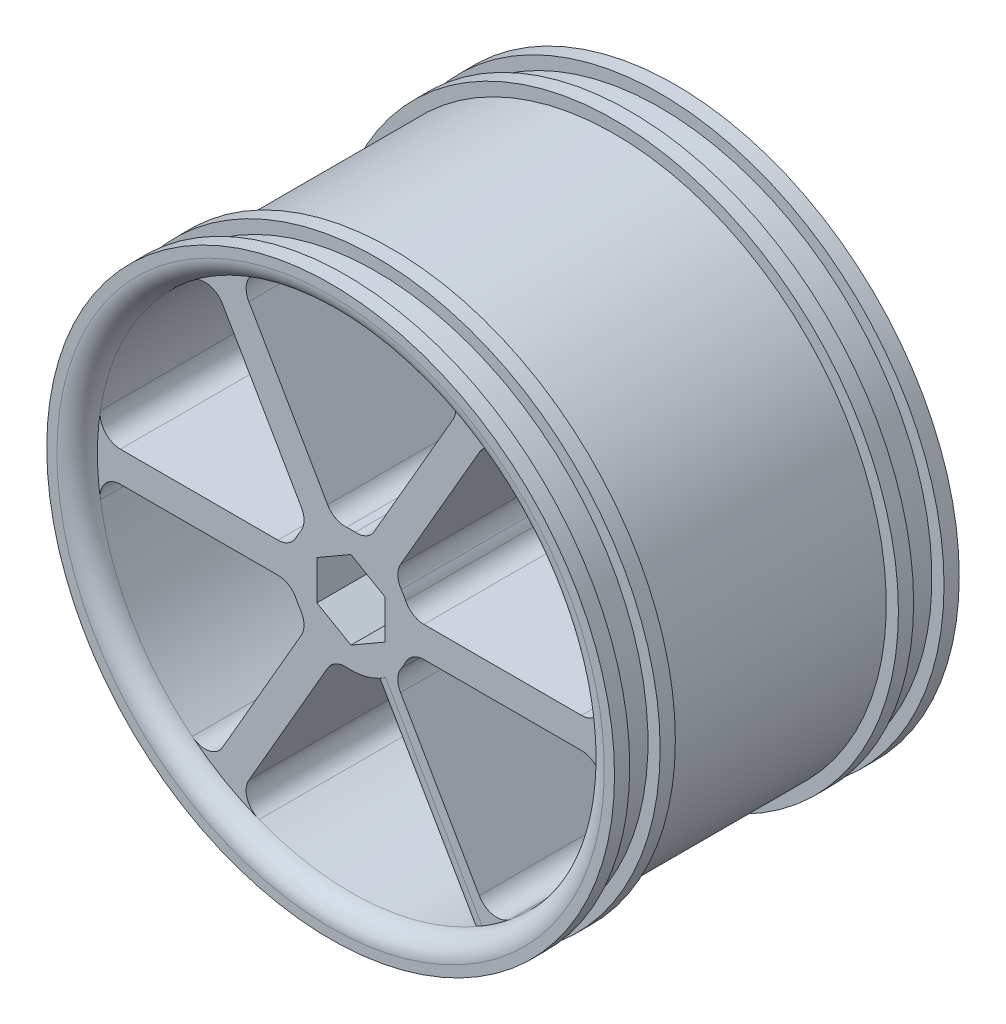
SolidWorks part; units mm, degrees
ref_plane "Front Plane" through (0, 0, 0) normal (0, 0, 1) x (1, 0, 0)
ref_plane "Top Plane" through (0, 0, 0) normal (0, 1, 0) x (1, 0, 0)
ref_plane "Right Plane" through (0, 0, 0) normal (1, 0, 0) x (0, 0, -1)
ref_plane "Plane1" through (0, 0, 0) normal (0, -1, 0) x (1, 0, 0)
sketch "Sketch1" plane through (0, 0, 0) normal (0, -1, 0) x (1, 0, 0)
  line L2 (25, 0) -> (28, 0)
  line L3 (28, 0) -> (28, 1.5)
  line L4 (28, 1.5) -> (26.8, 1.5)
  line L5 (26.8, 1.5) -> (26.8, 4.5)
  line L6 (26.8, 4.5) -> (28, 4.5)
  line L7 (28, 4.5) -> (28, 6)
  line L8 (28, 6) -> (26.8, 6)
  line L9 (26.8, 6) -> (26.8, 28)
  line L10 (26.8, 28) -> (28, 28)
  line L11 (28, 28) -> (28, 29.5)
  line L12 (28, 29.5) -> (26.8, 29.5)
  line L13 (26.8, 29.5) -> (26.8, 32.5)
  line L14 (26.8, 32.5) -> (28, 32.5)
  line L15 (28, 32.5) -> (28, 34)
  line L16 (0, 34) -> (0, 0) construction
  line L17 (25, 0) -> (25, 32)
  line L19 (0, 0) -> (25, 0) construction
  line L20 (27, 34) -> (28, 34)
  arc A0 (25, 32) -> (27, 34) centre (27, 32) cw
  dimension "D5" = 2
  dimension "D1" = 1.5
  dimension "D2" = 1.2
  dimension "D3" = 3
  dimension "D4" = 25
  dimension "D6" = 32
  dimension "D7" = 3
  dimension "D8" = 1.2
  dimension "D9" = 1.5
  dimension "D10" = 22
  dimension "D11" = 3
  dimension "D12" = 1.5
  dimension "D13" = 25
revolve "Revolve1" add sketch "Sketch1" angle 360 about L16
sketch "Sketch2" plane through (0, 0, 0) normal (0, 0, 1) x (1, 0, 0)
  line L0 (25, 0) -> (0, 0) construction
  line L1 (25, 1.5) -> (0, 1.5)
  line L2 (25, 1.5) -> (25, -1.5)
  line L3 (0, 1.5) -> (0, -1.5)
  line L4 (25, -1.5) -> (0, -1.5)
  line L5 (25, 1.5) -> (0, -1.5) construction
  line L6 (0, 1.5) -> (25, -1.5) construction
  circle A0 centre (0, 0) radius 25 construction
  circle A1 centre (0, 0) radius 25 construction
  point P3 (25, 0)
  point P6 (12.5, 0)
  dimension "D1" = 25
  dimension "D2" = 3
extrude "Boss-Extrude1" add sketch "Sketch2" along normal blind 32
pattern_circular "CirPattern1" count 6 over 360 about axis through (0, 0, 0) along (0, 0, 1) of "Boss-Extrude1"
sketch "Sketch5" plane through (0, 0, 0) normal (0, 0, 1) x (1, 0, 0)
  circle A0 centre (0, 0) radius 6
  dimension "D1" = 12
extrude "Boss-Extrude2" add sketch "Sketch5" along normal blind 32
sketch "Sketch6" plane through (0, 0, 0) normal (0, 0, 1) x (1, 0, 0)
  line L0 (0, 0) -> (0, 12.204) construction
  line L5 (0, -3.87) -> (3.3515, -1.935)
  line L6 (3.3515, -1.935) -> (3.3515, 1.935)
  line L7 (3.3515, 1.935) -> (0, 3.87)
  line L8 (0, 3.87) -> (-3.3515, 1.935)
  line L9 (-3.3515, 1.935) -> (-3.3515, -1.935)
  line L10 (-3.3515, -1.935) -> (0, -3.87)
  circle A0 centre (0, 0) radius 3.3515 construction
  dimension "D1" = 3.87
extrude "AxleHole" cut sketch "Sketch6" along normal through all
fillet "Fillet1" radius 2 22 edges at (-24.955, -1.5, 16) (-13.7765, -20.8616, 16) (-11.1784, -22.3616, 16) (13.7765, 20.8616, 16) (13.7765, -20.8616, 16) (5.8095, 1.5, 16) (4.2038, 4.2812, 16) (5.8095, -1.5, 16) (4.2038, -4.2812, 16) (1.6057, 5.7812, 16) (-1.6057, 5.7812, 16) (-4.2038, 4.2812, 16) (-5.8095, 1.5, 16) (-5.8095, -1.5, 16) (-4.2038, -4.2812, 16) (-1.6057, -5.7812, 16) (24.955, 1.5, 16) (24.955, -1.5, 16) (11.1784, 22.3616, 16) (-11.1784, 22.3616, 16) (-13.7765, 20.8616, 16) (-24.955, 1.5, 16)
